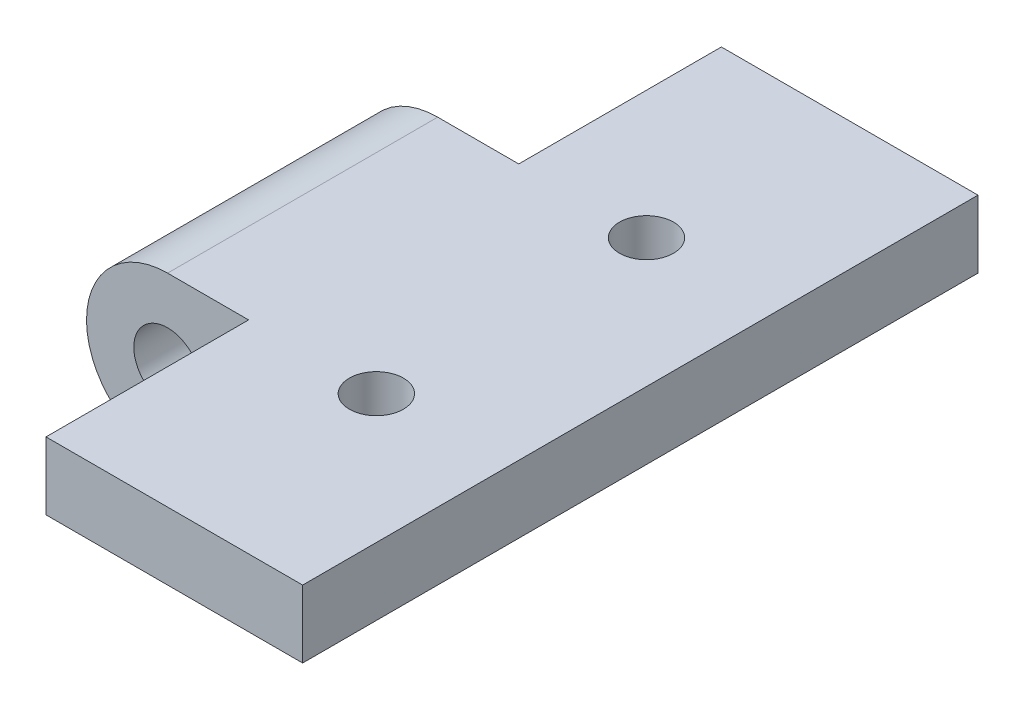
SolidWorks part; units mm, degrees
ref_plane "前基準面" through (0, 0, 0) normal (0, 0, 1) x (1, 0, 0)
ref_plane "上基準面" through (0, 0, 0) normal (0, 1, 0) x (1, 0, 0)
ref_plane "右基準面" through (0, 0, 0) normal (1, 0, 0) x (0, 0, -1)
sketch "草圖1" plane through (0, 0, 0) normal (0, 0, 1) x (1, 0, 0)
  circle A0 centre (0, 0) radius 6
  circle A1 centre (0, 0) radius 2.5
  dimension "D1" = 12
  dimension "D2" = 5
extrude "填料-伸長1" add sketch "草圖1" along normal blind 50
sketch "草圖2" plane through (0, 0, 50) normal (0, 0, 1) x (1, 0, 0)
  line L0 (0, 0) -> (0, 1) construction
  line L1 (-25, 6) -> (25, 6)
  line L2 (-25, 6) -> (-25, 1)
  line L3 (-25, 1) -> (25, 1)
  line L4 (25, 6) -> (25, 1)
  circle A0 centre (0, 0) radius 6 construction
  dimension "D1" = 50
  dimension "D2" = 5
extrude "填料-伸長2" add sketch "草圖2" against normal up to surface (50 mm away)
sketch "草圖3" plane through (0, 0, 0) normal (0, 0, -1) x (-1, 0, 0)
  circle A0 centre (0, 0) radius 2.5
  arc A1 (-2.2913, 1) -> (2.2913, 1) centre (0, 0) ccw construction
extrude "除料-伸長1" cut sketch "草圖3" against normal up to surface (50 mm away)
sketch "草圖8" plane through (0, 1, 0) normal (0, -1, 0) x (1, 0, 0)
  line L0 (25, 25) -> (-10.8762, 25) construction
  line L1 (25, 0) -> (25, 50) construction
  line L2 (15.458, 0) -> (15.458, 15) construction
  line L3 (25, 0) -> (5.9161, 0) construction
  line L4 (0, 0) -> (0, 22.7278) construction
  circle A0 centre (15.458, 35) radius 2
  circle A1 centre (15.458, 15) radius 2
  circle A2 centre (-15.458, 15) radius 2
  circle A3 centre (-15.458, 35) radius 2
  dimension "D1" = 20
  dimension "D2" = 4
extrude "除料-伸長6" cut sketch "草圖8" against normal up to next
sketch "草圖4" plane through (0, 1, 0) normal (0, -1, 0) x (1, 0, 0)
  line L0 (6, 50) -> (6, 35)
  line L1 (6, 0) -> (6, 50) construction
  line L2 (6, 35) -> (-6, 35)
  line L3 (-6, 50) -> (-6, 0) construction
  line L4 (-6, 35) -> (-6, 15)
  line L5 (-6, 15) -> (6, 15)
  line L6 (6, 15) -> (6, 0)
  line L7 (-6, 25) -> (25, 25) construction
  line L8 (25, 0) -> (25, 50) construction
  dimension "D1" = 20
extrude "除料-伸長2" [suppressed] cut sketch "草圖4" against normal through all and the other way through all
sketch "草圖5" [suppressed] plane through (0, 0, 50) normal (0, 0, 1) x (1, 0, 0)
  line L0 (0, 6) -> (6, 6)
  line L1 (6, 6) -> (6, 0)
  circle A0 centre (0, 0) radius 6
  line M2 (5.9161, 1) -> (6, 1)
  line M3 (6, 1) -> (6, 6)
  line M4 (6, 6) -> (-25, 6)
extrude "除料-伸長3" [suppressed] cut sketch "草圖5" against normal up to surface (50 mm away) contours A0 M2 M3 M4
extrude "除料-伸長4" cut sketch "草圖4<2>" against normal through all and the other way through all flip side to cut
sketch "草圖4<2>" plane through (0, 1, 0) normal (0, -1, 0) x (1, 0, 0) same geometry as "草圖4"
sketch "草圖6" plane through (0, 0, 35) normal (0, 0, 1) x (1, 0, 0)
  line L0 (0, 6) -> (-6, 6)
  line L1 (-6, 6) -> (-6, 0)
  circle A0 centre (0, 0) radius 6
  line M3 (6, 6) -> (-6, 6)
  line M4 (-6, 6) -> (-6, 1)
  line M5 (-6, 1) -> (-5.9161, 1)
extrude "除料-伸長5" cut sketch "草圖6" against normal up to next contours A0 M3 M4 M5 region at (-4.655, 4.674, 35)
